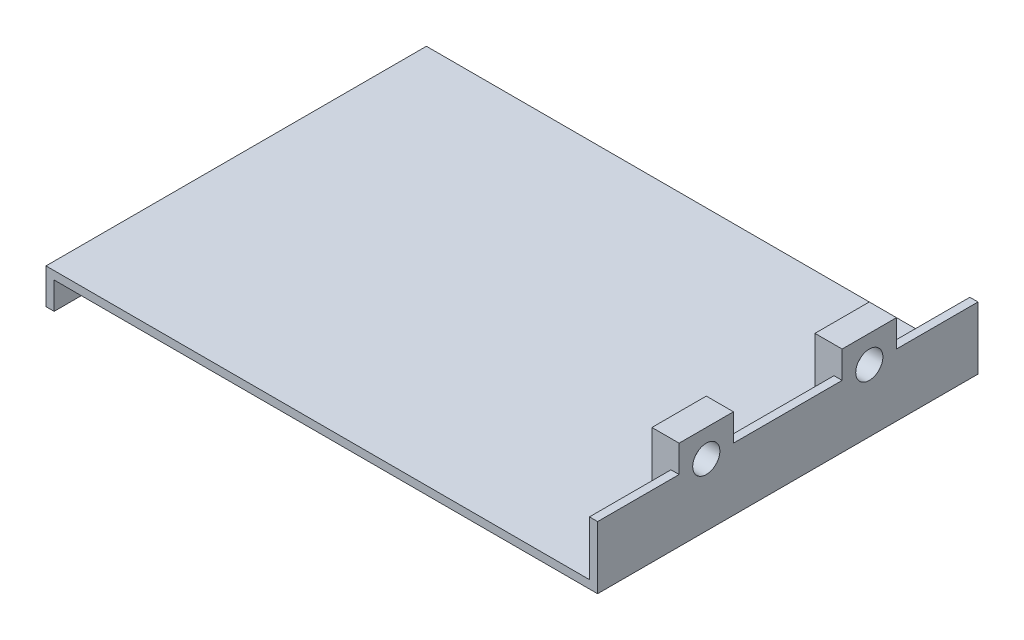
SolidWorks part; units mm, degrees
ref_plane "Front" through (0, 0, 0) normal (0, 0, 1) x (1, 0, 0)
ref_plane "Top" through (0, 0, 0) normal (0, 1, 0) x (1, 0, 0)
ref_plane "Right" through (0, 0, 0) normal (1, 0, 0) x (0, 0, -1)
other "Configuration Table"
sketch "Sketch1" plane through (0, 0, 0) normal (0, 1, 0) x (1, 0, 0)
  line L1 (-63.1519, 40.076) -> (36.8481, 40.076)
  line L2 (-63.1519, 40.076) -> (-63.1519, -29.924)
  line L3 (-63.1519, -29.924) -> (36.8481, -29.924)
  line L4 (36.8481, 40.076) -> (36.8481, -29.924)
  line L5 (-63.1519, 40.076) -> (-64.6519, 40.076)
  line L6 (-63.1519, 40.076) -> (-63.1519, -29.924)
  line L7 (-63.1519, -29.924) -> (-64.6519, -29.924)
  line L8 (-64.6519, 40.076) -> (-64.6519, -29.924)
  line L9 (36.8481, 40.076) -> (35.3481, 40.076)
  line L10 (36.8481, 40.076) -> (36.8481, -29.924)
  line L11 (36.8481, -29.924) -> (35.3481, -29.924)
  line L12 (35.3481, 40.076) -> (35.3481, -29.924)
  dimension "D1" = 70
  dimension "D2" = 100
  dimension "D3" = 1.5
  dimension "D4" = 1.5
extrude "Boss-Extrude1" add sketch "Sketch1" against normal blind 5 contours L5 L8 L7 L6
extrude "Boss-Extrude2" add sketch "Sketch1<3>" along normal blind 1.5 contours L12 L1 L2 L3 | L5 L8 L7 L6 | L9 L12 L11 L10 region at (-13.9019, 0, -5.076)
sketch "Sketch1<3>" plane through (0, 0, 0) normal (0, 1, 0) x (1, 0, 0) same geometry as "Sketch1"
extrude "Boss-Extrude3" add sketch "Sketch1<4>" along normal blind 10 from surface contours L9 L12 L11 L10 starting at face at (-13.9019, 1.5, -5.076)
sketch "Sketch1<4>" plane through (0, 0, 0) normal (0, 1, 0) x (1, 0, 0) same geometry as "Sketch1"
sketch "Sketch2" plane through (36.8481, 0, 0) normal (1, 0, 0) x (0, 0, -1)
  line L0 (5.076, 0) -> (5.076, 25) construction
  line L1 (40.076, 0) -> (-29.924, 0) construction
  line L2 (-29.924, 11.5) -> (40.076, 11.5) construction
  line L3 (-4.924, 11.5) -> (-14.924, 11.5)
  line L4 (-4.924, 11.5) -> (-4.924, 16.5)
  line L5 (-4.924, 16.5) -> (-14.924, 16.5)
  line L6 (-14.924, 11.5) -> (-14.924, 16.5)
  line L7 (15.076, 11.5) -> (15.076, 16.5)
  line L8 (15.076, 16.5) -> (25.076, 16.5)
  line L9 (25.076, 11.5) -> (25.076, 16.5)
  line L10 (15.076, 11.5) -> (25.076, 11.5)
  line L11 (25.076, 6.5) -> (15.076, 6.5)
  line L12 (-14.924, 11.5) -> (-4.924, 11.5)
  line L13 (-14.924, 11.5) -> (-14.924, 6.5)
  line L14 (-14.924, 6.5) -> (-4.924, 6.5)
  line L15 (-4.924, 11.5) -> (-4.924, 6.5)
  line L16 (15.076, 11.5) -> (15.076, 6.5)
  line L17 (25.076, 11.5) -> (15.076, 11.5)
  line L18 (25.076, 11.5) -> (25.076, 6.5)
  line L20 (-14.924, 6.5) -> (-4.924, 6.5)
  line L21 (-14.924, 6.5) -> (-14.924, 1.5)
  line L22 (-14.924, 1.5) -> (-4.924, 1.5)
  line L23 (-4.924, 6.5) -> (-4.924, 1.5)
  line L24 (15.076, 6.5) -> (25.076, 6.5)
  line L25 (15.076, 6.5) -> (15.076, 1.5)
  line L26 (15.076, 1.5) -> (25.076, 1.5)
  line L27 (25.076, 6.5) -> (25.076, 1.5)
  line M3 (40.076, 11.5) -> (-29.924, 11.5)
  dimension "D1" = 25
  dimension "D2" = 5
  dimension "D3" = 10
  dimension "D4" = 10
  dimension "D5" = 5
  dimension "D6" = 5
  dimension "D7" = 10
  dimension "D8" = 5
  dimension "D9" = 10
extrude "Boss-Extrude4" add sketch "Sketch2" against normal blind 1.5 contours L6 L4 L5 M3 | L9 L8 L7 M3 region at (36.8481, 14, 9.924) region at (36.8481, 14, -20.076)
extrude "Boss-Extrude5" add sketch "Sketch2<4>" against normal blind 3.5 from surface contours L6 L4 L5 M3 | L15 L13 L14 M3 | L18 L16 L11 M3 | L9 L8 L7 M3 | L23 L14 L21 L22 | L27 L11 L25 L26 region at (36.8481, 9, 9.924) region at (36.8481, 14, 9.924) region at (36.8481, 14, -20.076) region at (36.8481, 9, -20.076) region at (36.8481, 4, 9.924) region at (36.8481, 4, -20.076) starting at face at (35.3481, 11.5, -5.076)
sketch "Sketch2<4>" plane through (36.8481, 0, 0) normal (1, 0, 0) x (0, 0, -1) same geometry as "Sketch2"
sketch "Sketch4" plane through (31.8481, 0, 0) normal (-1, 0, 0) x (0, 0, 1)
  line L0 (-25.076, 16.5) -> (-15.076, 16.5) construction
  line L1 (-25.076, 1.5) -> (-25.076, 16.5) construction
  line L2 (14.924, 16.5) -> (14.924, 1.5) construction
  line L5 (4.924, 16.5) -> (14.924, 16.5) construction
  circle A0 centre (-20.076, 11.5) radius 2.5
  circle A1 centre (-20.076, 11.5) radius 4.95
  circle A2 centre (9.924, 11.5) radius 2.5
  circle A3 centre (9.924, 11.5) radius 4.95
  point P14 (9.924, 16.5)
  dimension "D1" = 5
  dimension "D2" = 9.9
  dimension "D5" = 5
  dimension "D6" = 9.9
  dimension "D3" = 5
  dimension "D4" = 5
  dimension "D7" = 5
  dimension "D8" = 5
extrude "Cut-Extrude1" cut sketch "Sketch4" against normal blind 1.5
extrude "Cut-Extrude2" cut sketch "Sketch4<2>" against normal through all contours A0 | A2 region at (31.8481, 11.5, -20.076) region at (31.8481, 11.5, 9.924)
sketch "Sketch4<2>" plane through (31.8481, 0, 0) normal (-1, 0, 0) x (0, 0, 1) same geometry as "Sketch4"
